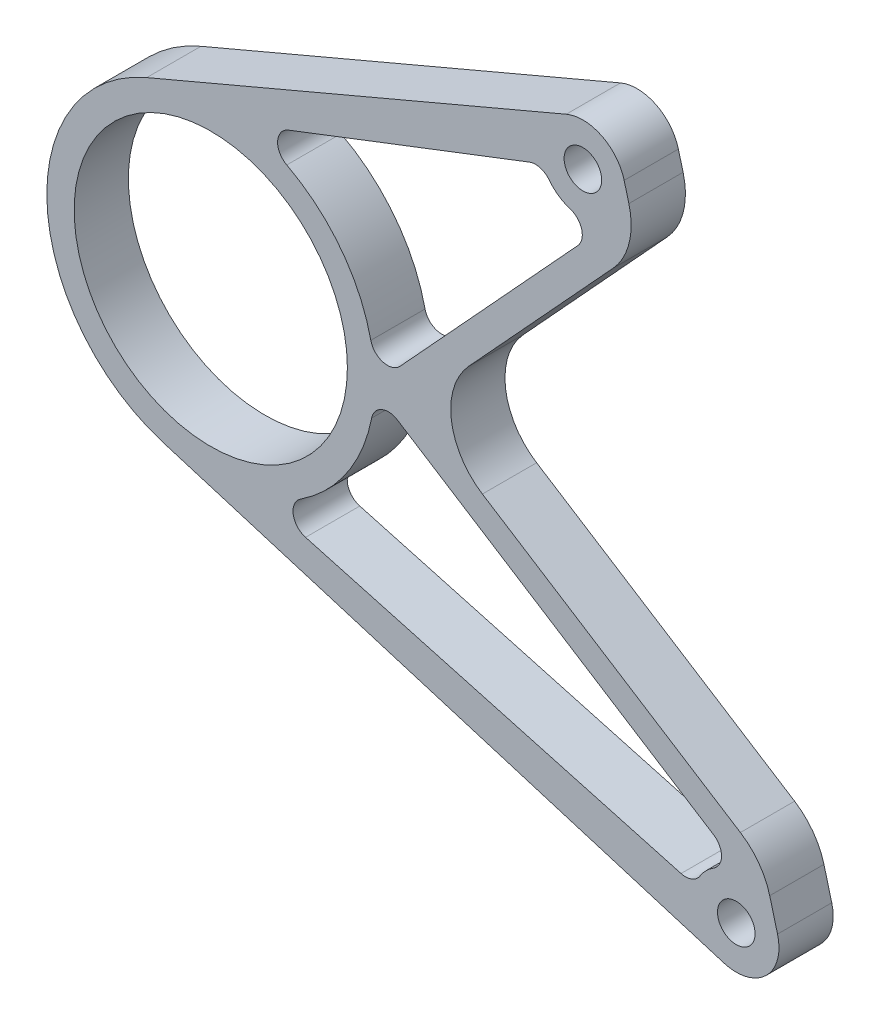
SolidWorks part; units mm, degrees
material "6061-T6 (SS)"
ref_plane "Front Plane" through (0, 0, 0) normal (0, 0, 1) x (1, 0, 0)
ref_plane "Top Plane" through (0, 0, 0) normal (0, 1, 0) x (1, 0, 0)
ref_plane "Right Plane" through (0, 0, 0) normal (1, 0, 0) x (0, 0, -1)
sketch "Sketch2" plane through (0, 0, 0) normal (0, 0, 1) x (1, 0, 0)
  line L0 (0, 0) -> (47.1306, -195.9686) construction
  line L1 (47.1306, -195.9686) -> (-302.8687, -196.6579) construction
  line L2 (-302.8687, -196.6579) -> (-257.3584, -0.3067) construction
  line L3 (-257.3584, -0.3067) -> (0, 0) construction
  line L4 (12.1535, 2.9229) -> (59.2841, -193.0457) construction
  line L5 (-12.1535, -2.9229) -> (34.9771, -198.8916) construction
  line L6 (0.0149, -12.5) -> (-257.3435, -12.8067) construction
  line L7 (-257.3733, 12.1933) -> (-0.0149, 12.5) construction
  line L8 (-269.5356, 2.5158) -> (-315.0459, -193.8355) construction
  line L9 (-290.6915, -199.4803) -> (-245.1812, -3.1291) construction
  line L10 (-302.8441, -209.1579) -> (47.1552, -208.4686) construction
  line L11 (-302.8933, -184.1579) -> (47.106, -183.4687) construction
  line L14 (-270.5025, 804.2833) -> (-527.997, 803.9765) construction
  line L15 (-558.0863, 605.6467) -> (-515.6688, 788.6542) construction
  circle A0 centre (0, 0) radius 12.5 construction
  circle A1 centre (47.1306, -195.9686) radius 12.5 construction
  circle A2 centre (-302.8687, -196.6579) radius 12.5 construction
  circle A3 centre (-257.3584, -0.3067) radius 12.5 construction
  circle A4 centre (-223.357, 595.8147) radius 12.5 construction
  arc A5 (-573.3809, 607.6254) -> (-573.3317, 582.6254) centre (-573.3563, 595.1254) ccw construction
sketch "Sketch4" plane through (0, 0, 0) normal (0, 0, 1) x (1, 0, 0)
  line L0 (-149.2073, -56.7645) -> (-5.3459, 11.2992) construction
  line L1 (-143.8125, -145.7054) -> (43.1897, -207.8311) construction
  line L2 (-128.6792, -100.1534) -> (47.1306, -195.9686) construction
  line L3 (12.1535, 2.9229) -> (59.2841, -193.0457) construction
  line L4 (-128.6792, -100.1534) -> (0, 0) construction
  line L5 (-142.6339, -146.0802) -> (21.5449, -195.9652)
  line L6 (37.2581, -180.7887) -> (-7.6495, -12.1388)
  line L7 (-24.6116, -3.8484) -> (-147.4299, -55.9673)
  line L8 (-257.3584, -0.3067) -> (0, 0) construction
  arc A0 (-149.2073, -56.7645) -> (-143.8125, -145.7054) centre (-128.6792, -100.1534) ccw construction
  arc A1 (-5.3459, 11.2992) -> (12.1535, 2.9229) centre (0, 0) cw construction
  arc A2 (43.1897, -207.8311) -> (59.2841, -193.0457) centre (47.1306, -195.9686) ccw construction
  circle A3 centre (47.1306, -195.9686) radius 12.5 construction
  circle A4 centre (0, 0) radius 12.5 construction
  circle A5 centre (-128.6792, -100.1534) radius 40 construction
  circle A6 centre (-128.6792, -100.1534) radius 121 construction
  circle A7 centre (-128.6792, -100.1534) radius 40
  arc A8 (-147.4299, -55.9673) -> (-142.6339, -146.0802) centre (-128.6792, -100.1534) ccw
  arc A9 (21.5449, -195.9652) -> (37.2581, -180.7887) centre (25.179, -184.0051) ccw
  arc A10 (-7.6495, -12.1388) -> (-24.6116, -3.8484) centre (-19.7286, -15.3552) ccw
  circle A11 centre (25.179, -184.0051) radius 5.5
  circle A12 centre (-19.7286, -15.3552) radius 5.5
  point P29 (-128.6792, -0.1533)
  dimension "D1" = 80
  dimension "D2" = 8
  dimension "D3" = 242
  dimension "D4" = 11
  dimension "D5" = 7
  dimension "D6" = 100
extrude "Boss-Extrude1" add sketch "Sketch4" along normal blind 15.875
sketch "Sketch5" plane through (0, 0, 15.875) normal (0, 0, 1) x (1, 0, 0)
  line L0 (-143.0483, -62.8234) -> (-19.7286, -15.3552)
  line L1 (-10.5248, -23.8132) -> (-80.6792, -100.1534)
  line L2 (-139.2976, -138.7183) -> (25.179, -184.0051)
  line L3 (-80.7084, -101.8286) -> (31.8884, -173.4584)
  line L4 (-128.6792, -100.1534) -> (-80.6792, -100.1534) construction
  line L5 (-80.7084, -101.8286) -> (-128.6792, -100.1534) construction
  circle A0 centre (-128.6792, -100.1534) radius 48
  arc A1 (-147.4299, -55.9673) -> (-142.6339, -146.0802) centre (-128.6792, -100.1534) ccw construction
  circle A2 centre (-19.7286, -15.3552) radius 12.5
  circle A3 centre (25.179, -184.0051) radius 12.5
  arc A4 (-7.6495, -12.1388) -> (-24.6116, -3.8484) centre (-19.7286, -15.3552) ccw construction
  circle A5 centre (-128.6792, -100.1534) radius 40 construction
  arc A6 (21.5449, -195.9652) -> (37.2581, -180.7887) centre (25.179, -184.0051) ccw construction
  dimension "D1" = 2
extrude "Cut-Extrude2" cut sketch "Sketch5" against normal through all contours A2 L0 A0 L1 | A3 L3 A0 L2 region at (-64.7358, -53.4499, 15.875) region at (-46.2329, -145.9947, 15.875)
fillet "Fillet1" radius 5 8 edges at (31.8884, -173.4584, 7.9375) (13.1274, -180.6869, 7.9375) (-80.7084, -101.8286, 7.9375) (-113.7166, -145.7617, 7.9375) (-80.6792, -100.1534, 7.9375) (-118.2864, -53.292, 7.9375) (-10.5248, -23.8132, 7.9375) (-31.3943, -19.8455, 7.9375)
sketch "Sketch6" plane through (0, 0, 15.875) normal (0, 0, 1) x (1, 0, 0)
  line L0 (-69.3062, -99.6006) -> (-3.4443, -27.9315)
  line L1 (37.2581, -180.7887) -> (-7.6495, -12.1388) construction
  line L2 (-69.3062, -99.6006) -> (32.9636, -164.6608)
  line L3 (32.9636, -164.6608) -> (-3.4443, -27.9315)
  line L4 (-21.2235, -35.4553) -> (-73.2525, -92.0719) construction
  line L5 (-73.981, -106.1083) -> (18.5477, -164.9716) construction
  line L6 (-44.0562, -72.1242) -> (-49.9466, -66.711) construction
  line L7 (-26.7207, -126.6919) -> (-31.0147, -133.4418) construction
  dimension "D1" = 8
extrude "Cut-Extrude3" cut sketch "Sketch6" against normal through all
fillet "Fillet2" radius 20 3 edges at (32.9636, -164.6608, 7.9375) (-69.3062, -99.6006, 7.9375) (-3.4443, -27.9315, 7.9375)
sketch "Sketch8" plane through (0, 0, 0) normal (0, 0, 1) x (1, 0, 0)
  line L0 (-257.3584, -0.3067) -> (-346.2284, -83.1582) construction
  line L1 (-346.2284, -83.1582) -> (-302.8687, -196.6579) construction
  circle A0 centre (-346.2284, -83.1582) radius 104 construction
  circle A1 centre (-257.3584, -0.3067) radius 12.5 construction
  circle A2 centre (-302.8687, -196.6579) radius 12.5 construction
  point P2 (-270.1586, -12.24)
  point P3 (-266.5014, -8.8305)
  point P5 (-309.1139, -180.3102)
  point P10 (-307.3296, -184.981)
  dimension "D1" = 208
  dimension "D2" = 5
  dimension "D3" = 5
